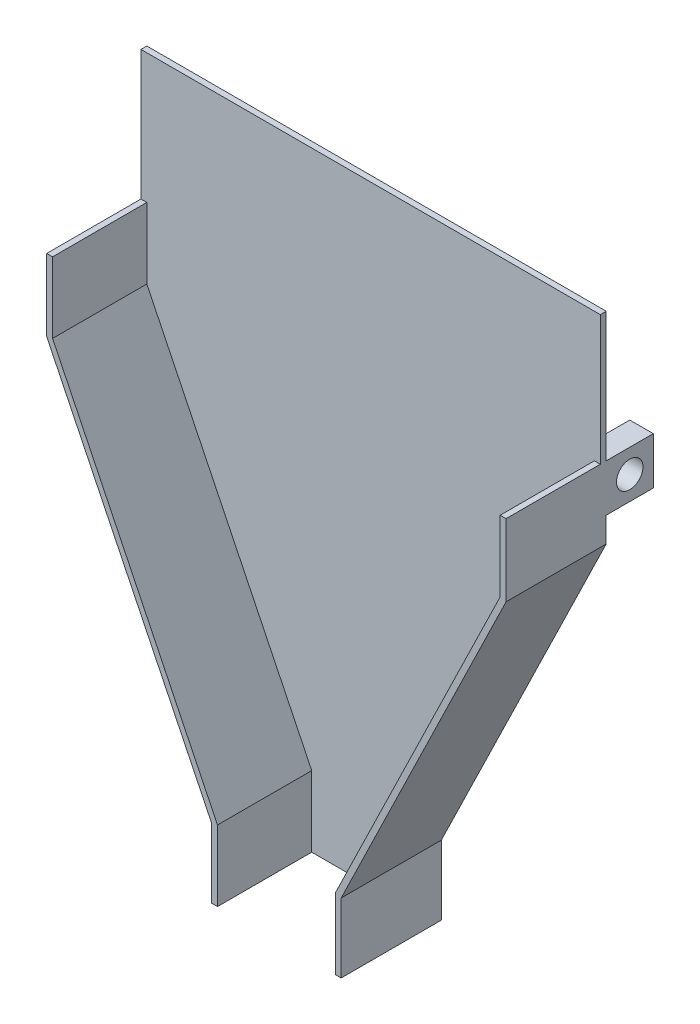
SolidWorks part; units mm, degrees
note: The reader was unsure of these and kept them because the rebuilt part matched: shared geometry of "Sketch1<3>".
ref_plane "Front Plane" through (0, 0, 0) normal (0, 0, 1) x (1, 0, 0)
ref_plane "Top Plane" through (0, 0, 0) normal (0, 1, 0) x (1, 0, 0)
ref_plane "Right Plane" through (0, 0, 0) normal (1, 0, 0) x (0, 0, -1)
sketch "Sketch1" plane through (0, 0, 0) normal (0, 0, 1) x (1, 0, 0)
  line L0 (0, 0) -> (0, 76.2)
  line L1 (0, 76.2) -> (177.8, 441.6424)
  line L5 (-304.8, 441.6424) -> (-127, 76.2)
  line L6 (-127, 76.2) -> (-127, 0)
  line L9 (-304.8, 441.6424) -> (-304.8, 517.8424)
  line L11 (177.8, 517.8424) -> (177.8, 441.6424)
  line L13 (-131.9609, 347.6536) -> (0, 76.4269) construction
  line L14 (-304.8, 517.8424) -> (177.8, 517.8424) construction
  line L16 (-127, 0) -> (0, 0) construction
  line L17 (-304.8, 517.8424) -> (177.8, 517.8424)
  line L19 (-127, 0) -> (0, 0)
  dimension "D1" = 76.2
  dimension "D2" = 127
  dimension "D3" = 301.625
  dimension "D4" = 114.3
  dimension "D5" = 406.4
  dimension "D6" = 0.2269
  dimension "D7" = 76.2
  dimension "D8" = 482.6
  dimension "D9" = 154.056
extrude "Extrude-Thin1" add sketch "Sketch1" along normal blind 101.6 and the other way blind 6.35 thin contours L9 L5 L6 | L0 L1 L11
extrude "Boss-Extrude1" add sketch "Sketch1<3>" against normal blind 6.35
sketch "Sketch1<3>" plane through (0, 0, 0) normal (0, 0, 1) x (1, 0, 0) same geometry as "Sketch1"
sketch "Sketch2" plane through (0, 0, -6.35) normal (0, 0, -1) x (-1, 0, 0)
  line L1 (-184.15, 517.8424) -> (-158.75, 517.8424)
  line L2 (-184.15, 517.8424) -> (-184.15, 467.0424)
  line L3 (-184.15, 467.0424) -> (-158.75, 467.0424)
  line L4 (-158.75, 517.8424) -> (-158.75, 467.0424)
  line L5 (311.15, 517.8424) -> (285.75, 517.8424)
  line L6 (311.15, 517.8424) -> (311.15, 467.0424)
  line L7 (311.15, 467.0424) -> (285.75, 467.0424)
  line L8 (285.75, 517.8424) -> (285.75, 467.0424)
  dimension "D1" = 25.4
  dimension "D2" = 50.8
extrude "Boss-Extrude2" add sketch "Sketch2" along normal blind 50.8
sketch "Sketch3" plane through (184.15, 0, 0) normal (1, 0, 0) x (0, 0, -1)
  line L0 (57.15, 517.8424) -> (57.15, 467.0424) construction
  line L1 (6.35, 467.0424) -> (6.35, 517.8424) construction
  line L2 (57.15, 517.8424) -> (-101.6, 517.8424) construction
  circle A0 centre (31.75, 492.4424) radius 14.2875
  point P4 (57.15, 492.4424)
  dimension "D1" = 28.575
  dimension "D2" = 25.4
extrude "Cut-Extrude1" cut sketch "Sketch3" against normal through all
sketch "Sketch4" plane through (0, 517.8424, 0) normal (0, 1, 0) x (1, 0, 0)
  line L0 (-311.15, 57.15) -> (-311.15, -101.6) construction
  line L1 (-311.15, 0) -> (184.15, 0)
  line L2 (-311.15, 0) -> (-311.15, 6.35)
  line L3 (-311.15, 6.35) -> (184.15, 6.35)
  line L4 (184.15, 0) -> (184.15, 6.35)
  line L5 (-304.8, 0) -> (177.8, 0) construction
  point P7 (-311.15, 1.9037)
extrude "Boss-Extrude3" add sketch "Sketch4" along normal blind 139.7
